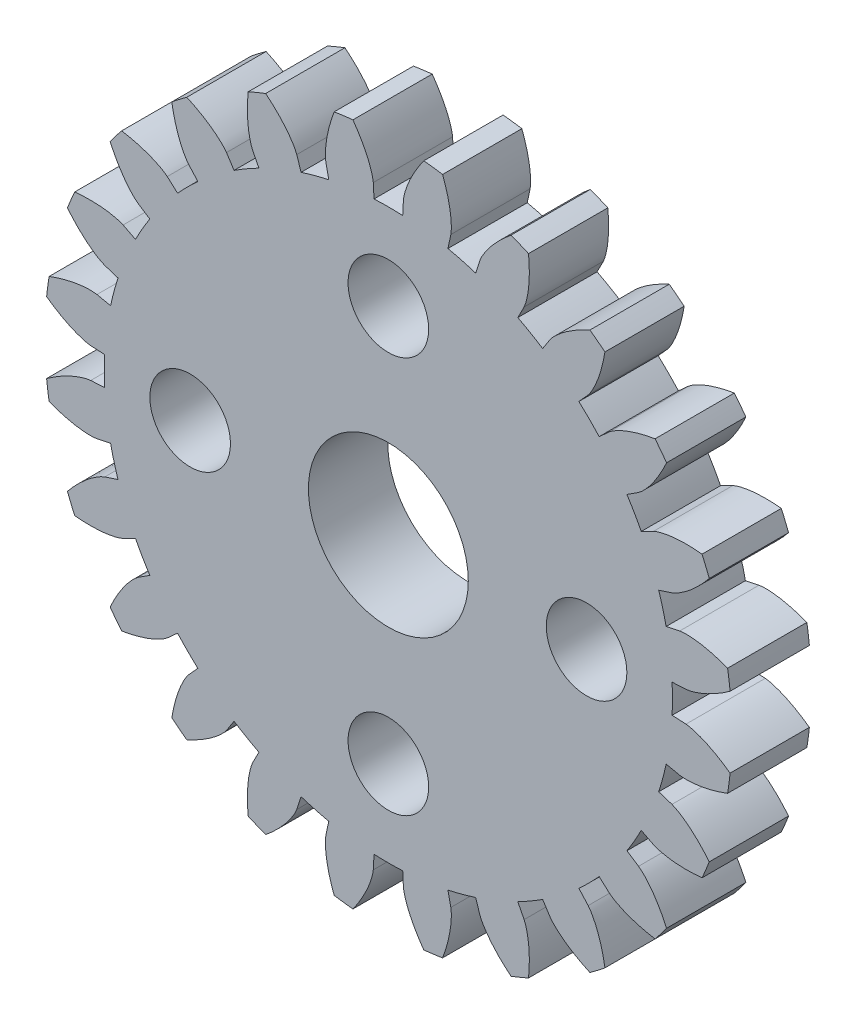
SolidWorks part; units mm, degrees
ref_plane "正面" through (0, 0, 0) normal (0, 0, 1) x (1, 0, 0)
ref_plane "平面" through (0, 0, 0) normal (0, 1, 0) x (1, 0, 0)
ref_plane "右側面" through (0, 0, 0) normal (1, 0, 0) x (0, 0, -1)
sketch "インボリュート スケッチ" plane through (0, 0, 0) normal (0, 0, 1) x (1, 0, 0)
  line L0 (-34.8106, -13.0518) -> (0.5697, -11.2619)
  line L1 (0.5697, -11.2619) -> (-0.5697, 11.2619) construction
  line L2 (0, 0) -> (0, 13) construction
  line L3 (-0.5697, 11.2619) -> (-0.5431, 10.7363)
  line L4 (0, 0) -> (0.5697, -11.2619)
  line L5 (-0.5431, 10.7363) -> (0, 10.7363)
  line L6 (0, 10.7363) -> (0, 0)
  circle A0 centre (0, 0) radius 11.2763 construction
  circle A1 centre (0, 0) radius 12 construction
  circle A2 centre (0, 0) radius 10.75 construction
  circle A3 centre (0, 0) radius 13 construction
  spline S0 degree 4 poles (-0.5697, 11.2619) (-0.574, 11.3046) (-0.5866, 11.3894) (-0.6249, 11.5484) (-0.6996, 11.7771) (-0.8595, 12.1613) (-1.1813, 12.7395) (-1.7152, 13.4541) (-2.5966, 14.3353) (-3.7723, 15.202) (-5.1872, 15.9587) (-6.8096, 16.5558) (-8.4923, 16.9475) (-10.208, 17.1468) (-12.02, 17.1664) (-14.2543, 16.9568) (-16.8688, 16.3668) (-19.7751, 15.2449) (-22.7719, 13.5148) (-25.4876, 11.3728) (-27.8885, 8.8847) (-29.6939, 6.4582) (-31.0213, 4.2351) (-31.9784, 2.3033) (-32.654, 0.7163) (-33.2393, -0.9057) (-33.7343, -2.5583) (-34.2406, -4.6529) (-34.5976, -6.7819) (-34.7866, -8.711) (-34.849, -10.3301) (-34.8576, -11.1858) (-34.8531, -11.7695) (-34.8449, -12.2259) (-34.821, -12.8723) (-34.7957, -13.354) (-34.7427, -14.1461) (-34.6848, -14.7539) (-34.6065, -15.4973) (-34.5193, -16.1547) (-34.4161, -16.8643) (-34.3018, -17.534) (-34.2052, -18.0593) (-34.1373, -18.3928) (-34.1019, -18.5662) knots 0 0 0 0 0 0.002802 0.005604 0.010661 0.015718 0.02996 0.048734 0.068727 0.096889 0.125051 0.153212 0.181374 0.209535 0.237696 0.271429 0.327752 0.384075 0.440398 0.496721 0.553044 0.609367 0.637529 0.66569 0.693852 0.722013 0.750174 0.778336 0.834659 0.86282 0.876901 0.883942 0.890982 0.900036 0.909091 0.920455 0.931818 0.943182 0.954545 0.965909 0.977273 0.988636 1 1 1 1 1 construction
  spline S1 degree 4 poles (-0.5697, 11.2619) (-0.574, 11.3046) (-0.5866, 11.3894) (-0.6249, 11.5484) (-0.6996, 11.7771) (-0.8595, 12.1613) (-1.1813, 12.7395) (-1.7152, 13.4541) (-2.5966, 14.3353) (-3.7723, 15.202) (-5.1872, 15.9587) (-6.8096, 16.5558) (-8.4923, 16.9475) (-10.208, 17.1468) (-12.02, 17.1664) (-14.2543, 16.9568) (-16.8688, 16.3668) (-19.7751, 15.2449) (-22.7719, 13.5148) (-25.4876, 11.3728) (-27.8885, 8.8847) (-29.6939, 6.4582) (-31.0213, 4.2351) (-31.9784, 2.3033) (-32.654, 0.7163) (-33.2393, -0.9057) (-33.7343, -2.5583) (-34.2406, -4.6529) (-34.5976, -6.7819) (-34.7866, -8.711) (-34.849, -10.3301) (-34.8576, -11.1858) (-34.8531, -11.7695) (-34.8449, -12.2259) (-34.8284, -12.6711) (-34.817, -12.926) (-34.8106, -13.0518) knots 0 0 0 0 0 0.002802 0.005604 0.010661 0.015718 0.02996 0.048734 0.068727 0.096889 0.125051 0.153212 0.181374 0.209535 0.237696 0.271429 0.327752 0.384075 0.440398 0.496721 0.553044 0.609367 0.637529 0.66569 0.693852 0.722013 0.750174 0.778336 0.834659 0.86282 0.876901 0.883942 0.890982 0.900036 0.909091 0.909091 0.909091 0.909091 0.909091
  point P6 (-0.7848, 11.9743)
  point P12 (0, 12)
  point P24 (0, 0)
  dimension "D1" = 22.5526
  dimension "D2" = 24
  dimension "D3" = 21.5
  dimension "D4" = 26
  dimension "D5" = 0.7854
extrude "インボリュート ボス" add sketch "インボリュート スケッチ" along normal blind 3 contours S1 L0 L4 region at (-15.8524, 0.743, 0)
mirror "インボリュート ミラー" about plane through (0, 0, 3) normal (1, 0, 0) of bodies 161
sketch "歯先円 スケッチ" plane through (0, 0, 3) normal (0, 0, 1) x (1, 0, 0)
  circle A0 centre (0, 0) radius 37.177
  circle A1 centre (0, 0) radius 13
  dimension "D1" = 26
extrude "歯先円 カット" cut sketch "歯先円 スケッチ" against normal through all
sketch "歯分割 スケッチ" plane through (0, 0, 3) normal (0, 0, 1) x (1, 0, 0)
  line L0 (-1.6968, 12.8888) -> (0, 0)
  line L1 (0, 0) -> (1.6968, 12.8888)
  line L2 (0, 0) -> (0, 12) construction
  arc A0 (-1.6968, 12.8888) -> (1.6968, 12.8888) centre (0, 0) ccw
  circle A2 centre (0, 0) radius 12 construction
  arc A3 (-1.3415, 12.9306) -> (-5.8908, -11.5887) centre (0, 0) ccw construction
  point P9 (-1.5663, 11.8973)
  point P10 (1.5663, 11.8973)
  dimension "D1" = 24
  dimension "D2" = 3.1416
extrude "歯分割 カット" cut sketch "歯分割 スケッチ" against normal through all
pattern_circular "歯分割 円形コピー" count 24 over 360 about axis through (0, 0, 0) along (0, 0, 1) of bodies 166
sketch "歯底円 スケッチ" plane through (0, 0, 3) normal (0, 0, 1) x (1, 0, 0)
  circle A0 centre (0, 0) radius 10.75
  dimension "D1" = 21.5
extrude "歯底円 ボス" add sketch "歯底円 スケッチ" against normal through all
sketch "軸 丸穴 スケッチ" plane through (0, 0, 3) normal (0, 0, 1) x (1, 0, 0)
  circle A0 centre (0, 0) radius 3.025
  dimension "D1" = 6.05
extrude "軸 丸穴 カット" cut sketch "軸 丸穴 スケッチ" against normal through all
sketch "軸 キー溝 スケッチ" plane through (0, 0, 3) normal (0, 0, 1) x (1, 0, 0)
  line L2 (-1.5, 3.7081) -> (-1.5, 5.4)
  line L3 (-1.5, 5.4) -> (1.5, 5.4)
  line L4 (1.5, 3.7081) -> (1.5, 5.4)
  arc A0 (-1.5, 3.7081) -> (1.5, 3.7081) centre (0, 0) ccw
  dimension "D1" = 8
  dimension "D2" = 3
  dimension "D3" = 5.4
extrude "軸 キー溝 カット" [suppressed] cut sketch "軸 キー溝 スケッチ" against normal through all
sketch "軸 Dカット スケッチ" plane through (0, 0, 3) normal (0, 0, 1) x (1, 0, 0)
  line L0 (-1.9861, 2) -> (1.9861, 2)
  arc A0 (-2.3948, 1.8069) -> (2.3948, 1.8069) centre (0, 0) ccw
  arc A1 (-1.9861, 2) -> (-2.3948, 1.8069) centre (-2.2361, 2) ccw
  arc A2 (2.3948, 1.8069) -> (1.9861, 2) centre (2.2361, 2) ccw
  dimension "D1" = 6
  dimension "D3" = 0.5
  dimension "D2" = 2
extrude "軸 Dカット カット" [suppressed] cut sketch "軸 Dカット スケッチ" against normal through all
sketch "軸 角穴 スケッチ" plane through (0, 0, 3) normal (0, 0, 1) x (1, 0, 0)
  line L0 (-5.1, 5.1) -> (5.1, 5.1)
  line L1 (-5, -5) -> (5, -5) construction
  line L2 (-5, -5) -> (-5, 5) construction
  line L3 (-5, 5) -> (5, 5) construction
  line L4 (5, -5) -> (5, 5) construction
  line L5 (-5, -5) -> (5, 5) construction
  line L6 (-5, 5) -> (5, -5) construction
  line L7 (5.1, -5.1) -> (5.1, 5.1)
  line L8 (-5.1, -5.1) -> (5.1, -5.1)
  line L9 (-5.1, -5.1) -> (-5.1, 5.1)
  point P0 (0, 0)
  dimension "D1" = 10
  dimension "D2" = 0.1
extrude "軸 角穴 カット" [suppressed] cut sketch "軸 角穴 スケッチ" against normal through all
sketch "フランジ穴 スケッチ" plane through (0, 0, 3) normal (0, 0, 1) x (1, 0, 0)
  circle A0 centre (0, 12) radius 1.6
  circle A1 centre (12, 0) radius 1.6
  circle A2 centre (0, -12) radius 1.6
  circle A3 centre (-12, 0) radius 1.6
  point P12 (0, 0)
  dimension "D2" = 3.2
  dimension "D3" = 12
  dimension "D1" = 4
extrude "フランジ穴 カット" [suppressed] cut sketch "フランジ穴 スケッチ" against normal through all
sketch "合致用スケッチ" plane through (0, 0, 3) normal (0, 0, 1) x (1, 0, 0)
  line L0 (0, 0) -> (0, 12)
  line L1 (0, 0) -> (1.5663, 11.8973)
  circle A2 centre (0, 0) radius 12
  dimension "D1" = 24
  dimension "D2" = 7.5
sketch "ｽｹｯﾁ1" plane through (0, 0, 3) normal (0, 0, 1) x (1, 0, 0)
  line L0 (0, 0) -> (7.5, 0) construction
  line L1 (0, 0) -> (0, -7.5) construction
  line L2 (0, 0) -> (-7.5, 0) construction
  line L3 (0, 0) -> (0, 7.5) construction
  circle A0 centre (7.5, 0) radius 1.525
  circle A1 centre (0, -7.5) radius 1.525
  circle A2 centre (-7.5, 0) radius 1.525
  circle A3 centre (0, 7.5) radius 1.525
  point P12 (0, 0)
  dimension "D1" = 3.05
  dimension "D2" = 7.5
  dimension "D3" = 4
extrude "ｶｯﾄ - 押し出し1" cut sketch "ｽｹｯﾁ1" against normal through all
equation "\"モジュール\"= 1"
equation "\"基準圧力角\"= 20"
equation "\"歯数\"= 24"
equation "\"基準円直径\"= \"歯数\" * \"モジュール\""
equation "\"基礎円直径\"= \"基準円直径\" * cos ( \"基準圧力角\" )"
equation "\"歯先円直径\"= \"基準円直径\" + 2 * \"モジュール\""
equation "\"歯底円直径\"= \"基準円直径\" - 2.5 * \"モジュール\""
equation "\"D1@インボリュート スケッチ\" = \"基礎円直径\""
equation "\"D2@インボリュート スケッチ\" = \"基準円直径\""
equation "\"D3@インボリュート スケッチ\" = \"歯底円直径\""
equation "\"D4@インボリュート スケッチ\" = \"歯先円直径\""
equation "\"D5@インボリュート スケッチ\" = Pi * \"モジュール\" / 4"
equation "\"D1@歯先円 スケッチ\" = \"歯先円直径\""
equation "\"D1@歯分割 スケッチ\" = \"基準円直径\""
equation "\"D2@歯分割 スケッチ\" = PI * \"モジュール\""
equation "\"D1@歯分割 円形コピー\" = \"歯数\""
equation "\"D1@歯底円 スケッチ\" = \"歯底円直径\""
equation "\"板厚\"= 3"
equation "\"D1@インボリュート ボス\"=\"板厚\""
equation "\"D1@合致用スケッチ\" = \"基準円直径\""
equation "\"D2@合致用スケッチ\"=180/\"歯数\""
